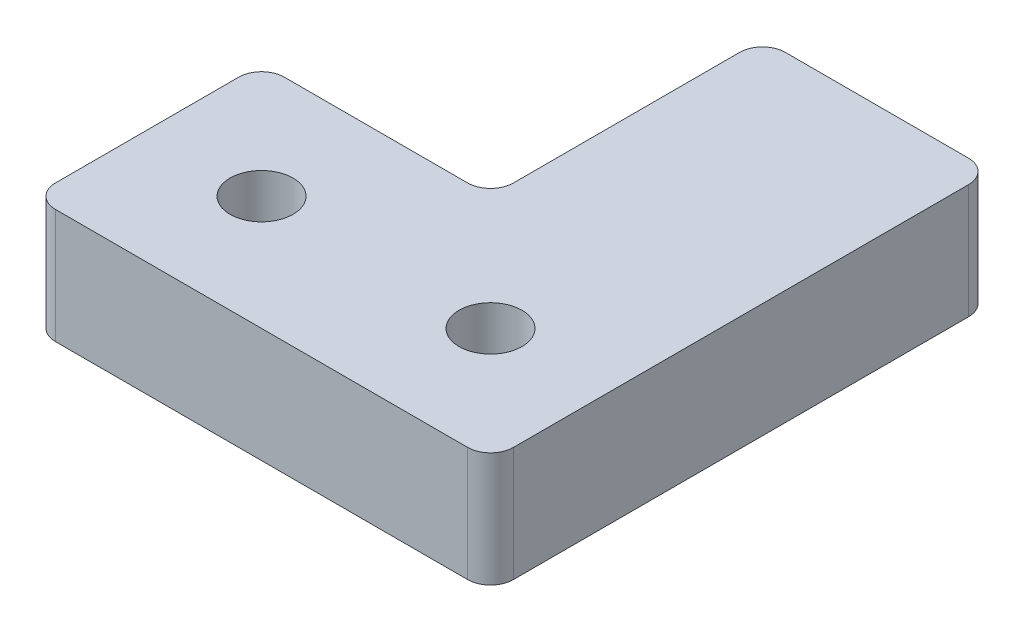
SolidWorks part; units mm, degrees
ref_plane "Front Plane" through (0, 0, 0) normal (0, 0, 1) x (1, 0, 0)
ref_plane "Top Plane" through (0, 0, 0) normal (0, 1, 0) x (1, 0, 0)
ref_plane "Right Plane" through (0, 0, 0) normal (1, 0, 0) x (0, 0, -1)
sketch "Sketch1" plane through (0, 0, 0) normal (0, 1, 0) x (1, 0, 0)
  line L0 (0, 0) -> (40, 0)
  line L1 (40, 0) -> (40, 43.75)
  line L2 (40, 43.75) -> (20, 43.75)
  line L3 (20, 43.75) -> (20, 20)
  line L4 (20, 20) -> (0, 20)
  line L5 (0, 20) -> (0, 0)
  dimension "D1" = 20
  dimension "D2" = 40
  dimension "D3" = 20
  dimension "D4" = 23.75
extrude "Boss-Extrude1" add sketch "Sketch1" along normal blind 10
sketch "Sketch2" plane through (0, 0, 0) normal (0, -1, 0) x (1, 0, 0)
  line L0 (0, -10) -> (40, -10)
  line L1 (0, -20) -> (0, 0) construction
  line L2 (40, 0) -> (40, -43.75) construction
  point P6 (10, -10)
  point P7 (30, -10)
  dimension "D1" = 10
  dimension "D2" = 10
hole_wizard "CBORE for M5 SHCS1" positions "Sketch3" profile "Sketch4" counterbore size "M5" standard "ANSI Metric" end condition through all
sketch "Sketch3" plane through (0, 0, 0) normal (0, -1, 0) x (-1, 0, 0)
  point P0 (-10, 10)
  point P3 (-30, 10)
sketch "Sketch4" plane through (10, 0, -10) normal (1, 0, 0) x (0, 0, -1)
  line L0 (0, 0) -> (0, 10)
  line L1 (0, 10) -> (2.75, 10)
  line L3 (2.75, 10) -> (2.75, 5)
  line L4 (5, 5) -> (2.75, 5)
  line L5 (5, 5) -> (5, 0.025)
  line L6 (5, 0.025) -> (5.025, 0)
  line L7 (5.025, 0) -> (0, 0)
  line L8 (-5, 0.025) -> (-5.025, 0) construction
  line L11 (0, -6.35) -> (0, 107.95) construction
  dimension "Thru Hole Dia." = 5.5
  dimension "Thru Hole Depth" = 10
  dimension "C'Bore Dia." = 10
  dimension "C'Bore Depth" = 5
  dimension "Near C'Sink Dia." = 10.05
  dimension "Near C'Sink Angle" = 90
fillet "Fillet1" radius 2 6 edges at (20, 5, -20) (20, 5, -43.75) (40, 5, -43.75) (0, 5, -20) (0, 5, 0) (40, 5, 0)
sketch "Sketch5" plane through (0, 10, 0) normal (0, 1, 0) x (1, 0, 0)
  line L0 (30, 43.75) -> (30, 0) construction
  line L1 (38, 43.75) -> (22, 43.75) construction
  line L2 (2, 0) -> (38, 0) construction
  line L3 (20, 33.75) -> (40, 33.75) construction
  circle A0 centre (30, 33.75) radius 1.5
  dimension "D1" = 3
  dimension "D2" = 10
